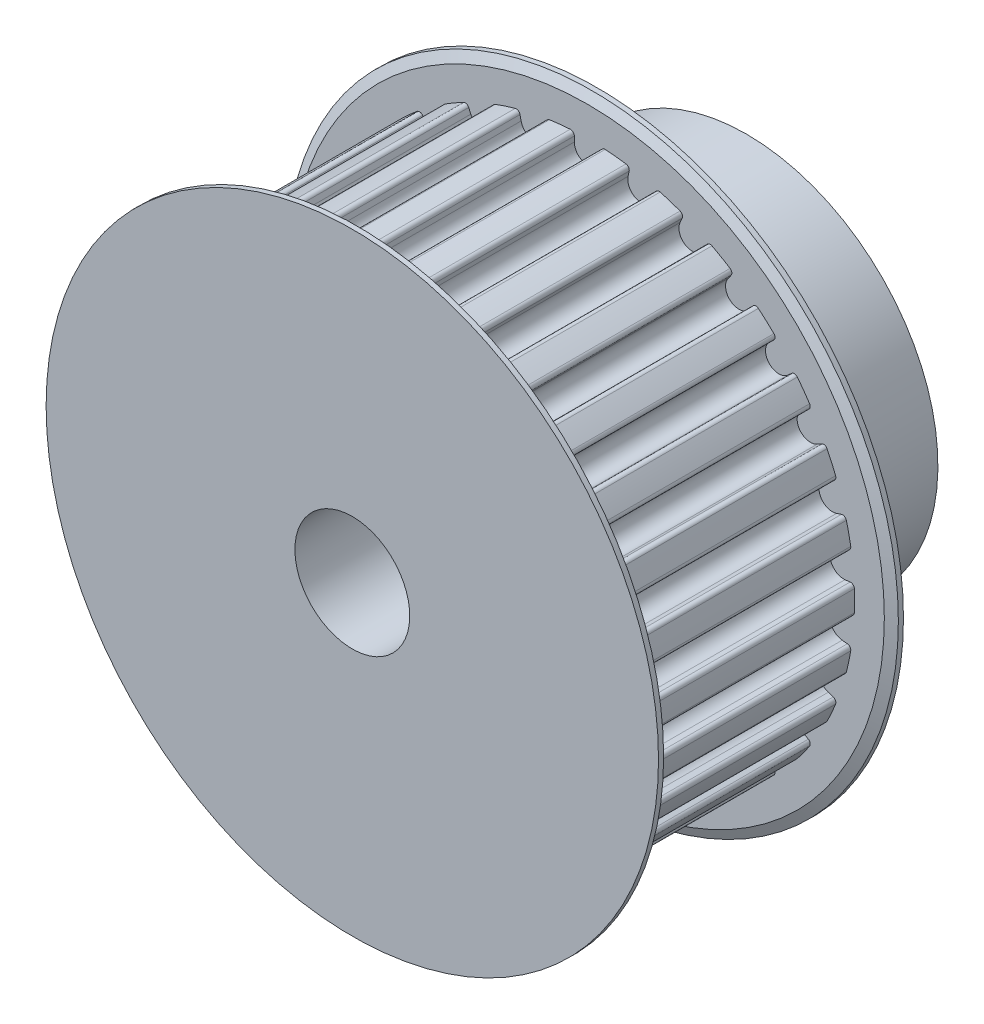
SolidWorks part; units mm, degrees
ref_plane "Front" through (0, 0, 0) normal (0, 0, 1) x (1, 0, 0)
ref_plane "Top" through (0, 0, 0) normal (0, 1, 0) x (1, 0, 0)
ref_plane "Right" through (0, 0, 0) normal (1, 0, 0) x (0, 0, -1)
sketch "support-front-body" plane through (0, 0, 0) normal (0, 0, 1) x (1, 0, 0)
  line L0 (0, 0) -> (0, 13.945) construction
  line L1 (0, 0) -> (0, -13.945) construction
  line L2 (0, 0) -> (13.945, 0) construction
  line L3 (0, 0) -> (-13.945, 0) construction
  circle A0 centre (0, 0) radius 13.945
  dimension "diam-outer" = 27.89
sketch "support-right-body" plane through (0, 0, 0) normal (1, 0, 0) x (0, 0, -1)
  line L0 (0, 0) -> (12.8, 0) construction
  line L1 (0, 13.945) -> (12.8, 13.945)
  line L2 (0, 13.945) -> (0, -13.945)
  line L3 (0, -13.945) -> (12.8, -13.945)
  line L4 (12.8, 13.945) -> (12.8, -13.945)
  dimension "length" = 12.8
sketch "support-right-chamfer" plane through (0, 0, 0) normal (1, 0, 0) x (0, 0, -1)
  line L0 (0, 0) -> (12.8, 0) construction
  line L1 (0, -13.945) -> (0, -12.945)
  line L2 (0, 13.945) -> (0, -13.945) construction
  line L4 (0, -12.945) -> (1, -13.945)
  line L5 (0, -13.945) -> (12.8, -13.945) construction
  line L7 (1, -13.945) -> (0, -13.945)
  line L9 (12.8, -13.945) -> (11.8, -13.945)
  line L11 (11.8, -13.945) -> (12.8, -12.945)
  line L12 (12.8, 13.945) -> (12.8, -13.945) construction
  line L14 (12.8, -12.945) -> (12.8, -13.945)
  dimension "height-chamfer-front" = 1
  dimension "angle-chamfer-front" = 45
  dimension "angle-chamfer-back" = 45
  dimension "height-chamfer-back" = 1
sketch "support-right-hub" plane through (0, 0, 0) normal (1, 0, 0) x (0, 0, -1)
  line L0 (20.6, 0) -> (12.8, 0) construction
  line L1 (12.8, 10) -> (20.6, 10)
  line L2 (12.8, 10) -> (12.8, -10)
  line L3 (12.8, -10) -> (20.6, -10)
  line L4 (20.6, 10) -> (20.6, -10)
  line L6 (0, 0) -> (12.8, 0) construction
  line L8 (0, 13.945) -> (0, -13.945) construction
  dimension "diam-hub" = 20
  dimension "length-hub" = 7.8
  dimension "dist-hub" = 12.8
sketch "support-right-bore" plane through (0, 0, 0) normal (1, 0, 0) x (0, 0, -1)
  line L0 (0, 13.945) -> (0, -13.945) construction
  line L1 (0, 3) -> (20.6, 3)
  line L2 (0, 3) -> (0, -3)
  line L3 (0, -3) -> (20.6, -3)
  line L4 (20.6, 3) -> (20.6, 0)
  line L5 (20.6, 0) -> (0, 0) construction
  line L6 (0, 0) -> (12.8, 0) construction
  line L7 (20.6, 0) -> (20.6, -3)
  line L8 (20.6, -3) -> (20.6, 3) construction
  dimension "diam-bore" = 6
  dimension "length-bore" = 20.6
  dimension "angle-bore-bottom" = 180
  dimension "angle-bore" = 90
sketch "support-stop-screw-hole" plane through (0, 0, 0) normal (1, 0, 0) x (0, 0, -1)
  line L1 (6.5667, 11) -> (9.4333, 11)
  line L2 (6.5667, 11) -> (6.5667, -1)
  line L3 (8, -1) -> (9.4333, -1)
  line L4 (9.4333, 11) -> (9.4333, -1)
  line L5 (8, -1) -> (8, 11) construction
  line L6 (8, -1) -> (6.5667, -1)
  line L7 (0, 0) -> (8, 0) construction
  line L8 (0, 13.945) -> (0, -13.945) construction
  dimension "diam-stop-screw-hole" = 2.8665
  dimension "dist-stop-screw-hole" = 8
  dimension "depth-stop-screw-hole" = 12
  dimension "angle-stop-screw-hole" = 180
  dimension "height-stop-screw-hole" = 11
sketch "support-front-keygroove" plane through (0, 0, 0) normal (0, 0, 1) x (1, 0, 0)
  line L0 (0, 0) -> (0, -3) construction
  line L1 (-1, 5) -> (1, 5)
  line L2 (-1, 5) -> (-1, 2.8)
  line L3 (-1, 2.8) -> (1, 2.8)
  line L4 (1, 5) -> (1, 2.8)
  line L5 (0, 0) -> (0, 3) construction
  circle A0 centre (0, 0) radius 3 construction
  dimension "width-keygroove" = 2
  dimension "dist-keygroove" = 8
  dimension "height-keygroove" = 2.2
sketch "support-front-tooth" plane through (0, 0, 0) normal (0, 0, 1) x (1, 0, 0)
  line L0 (0.7, 13.445) -> (0.7, 13.7155)
  line L1 (0, 0) -> (0, 13.945) construction
  line L2 (-0.7, 13.445) -> (-0.7, 13.7155)
  line L3 (0, 13.9151) -> (0, 13.945) construction
  line L8 (0, 13.9151) -> (0, 12.745) construction
  line L9 (0.9131, 13.9151) -> (-0.9131, 13.9151) construction
  line L10 (0, 13.9151) -> (0, 15.0851) construction
  line L17 (0.9131, 13.9151) -> (0.9131, 15.0851)
  line L21 (-0.9131, 15.0851) -> (-0.9131, 13.9151)
  line L22 (0.9131, 15.0851) -> (-0.9131, 15.0851)
  arc A0 (-0.7, 13.445) -> (0.7, 13.445) centre (0, 13.445) ccw
  circle A1 centre (0, 0) radius 13.945 construction
  arc A2 (0.7, 13.7155) -> (0.9131, 13.9151) centre (0.9, 13.7155) cw
  arc A3 (-0.7, 13.7155) -> (-0.9131, 13.9151) centre (-0.9, 13.7155) ccw
  circle A4 centre (0, 0) radius 13.945
  dimension "D3" = 0.2
  dimension "D2" = 0.7
  dimension "D1" = 1.2
sketch "support-right-flange" plane through (0, 0, 0) normal (1, 0, 0) x (0, 0, -1)
  line L0 (0, 6.9795) -> (0, 12.9932)
  line L1 (12.8, 13.945) -> (12.8, -13.945) construction
  line L2 (0, 12.9932) -> (0.5, 12.9932) construction
  line L3 (0.5, 12.9932) -> (0.5, 16)
  line L4 (0, 16) -> (0.5, 16)
  line L5 (0.5, 12.9932) -> (0.5, 6.9795)
  line L6 (0.5, 6.9795) -> (0, 6.9795)
  line L7 (6.4, 13.945) -> (6.4, 0) construction
  line L8 (0, 13.945) -> (12.8, 13.945) construction
  line L9 (0, 12.9932) -> (0, 16)
  line L10 (12.3, 6.9795) -> (12.8, 6.9795)
  line L11 (12.3, 12.9932) -> (12.3, 6.9795)
  line L12 (12.8, 16) -> (12.3, 16)
  line L13 (12.3, 12.9932) -> (12.3, 16)
  line L14 (12.8, 12.9932) -> (12.8, 16)
  line L15 (12.8, 6.9795) -> (12.8, 12.9932)
  line L16 (12.8, 0) -> (0, 0) construction
  line L17 (12.8, -6.9795) -> (12.8, -12.9932)
  line L18 (12.8, -12.9932) -> (12.8, -16)
  line L19 (12.3, -12.9932) -> (12.3, -16)
  line L20 (12.8, -16) -> (12.3, -16)
  line L21 (12.3, -12.9932) -> (12.3, -6.9795)
  line L22 (12.3, -6.9795) -> (12.8, -6.9795)
  line L23 (0.5, -6.9795) -> (0, -6.9795)
  line L24 (0.5, -12.9932) -> (0.5, -6.9795)
  line L25 (0, -16) -> (0.5, -16)
  line L26 (0.5, -12.9932) -> (0.5, -16)
  line L27 (0, -12.9932) -> (0, -16)
  line L28 (0, -6.9795) -> (0, -12.9932)
  line L29 (0, 0) -> (12.8, 0) construction
  line L30 (0, 12.9932) -> (0.5, 12.9932) construction
  line L31 (0.25, 6.9795) -> (0.25, 9.9863) construction
  line L32 (0.25, 9.9863) -> (0.25, 12.9932) construction
  line L33 (0.25, 16) -> (0.25, 12.9932) construction
  line L34 (0, 13.945) -> (12.8, 13.945) construction
  dimension "angle-flange" = 180
  dimension "thickness-flange" = 0.5
  dimension "diam-flange-inner" = 13.959
  dimension "diam-flange-outer" = 32
  dimension "width-flange-inner" = 11.8
sketch "support-right-flange-profile" plane through (0, 0, 0) normal (1, 0, 0) x (0, 0, -1)
  line L0 (0.2668, 16) -> (0.5, 16)
  line L2 (0.5, 16) -> (0.5, 15.5)
  line L3 (0.5, 12.9932) -> (0.5, 6.9795) construction
  line L4 (0.5, 15.5) -> (0.2668, 16)
  line L5 (0, 0) -> (12.8, 0) construction
  line L6 (6.4, 0) -> (6.4, 13.945) construction
  line L7 (12.3, 15.5) -> (12.5332, 16)
  line L8 (12.3, 16) -> (12.3, 15.5)
  line L9 (12.5332, 16) -> (12.3, 16)
  dimension "D1" = 25
  dimension "D2" = 0.5
ref_axis "ref-axis-center" through (0, 0, -12.8) along (0, 0, 1)
ref_plane "ref-plane-front" through (0, 0, 0) normal (0, 0, 1) x (1, 0, 0)
ref_plane "ref-plane-back" through (0, 0, -12.8) normal (0, 0, 1) x (1, 0, 0)
ref_plane "ref-plane-hub-front" through (0, 0, -12.8) normal (0, 0, 1) x (1, 0, 0)
ref_plane "ref-plane-hub-back" through (0, 0, -20.6) normal (0, 0, 1) x (1, 0, 0)
ref_plane "ref-plane-bore-front" through (0, 0, 0) normal (0, 0, 1) x (1, 0, 0)
ref_plane "ref-plane-bore-back" through (0, 0, -20.6) normal (0, 0, 1) x (1, 0, 0)
ref_plane "ref-plane-stop-screw-hole-top" through (0, 11, 0) normal (0, 1, 0) x (-1, 0, 0)
ref_axis "ref-axis-stop-screw-hole" through (0, 11, -8) along (0, -1, 0)
sketch "Sketch5" plane through (0, 0, 0) normal (1, 0, 0) x (0, 0, -1)
  line L0 (12.8, 13.945) -> (12.8, -13.945) construction
  line L1 (0, 13.945) -> (12.8, 13.945) construction
  line L2 (0, 13.945) -> (0, -13.945) construction
  line L3 (0, 0) -> (12.8, 0) construction
  line L4 (12.8, 13.945) -> (12.8, 0)
  line L5 (0, 13.945) -> (12.8, 13.945)
  line L6 (0, 13.945) -> (0, 0)
  line L7 (0, 0) -> (12.8, 0) construction
  line L8 (0, 0) -> (12.8, 0)
  dimension "D1" = 12.8
revolve "body" add sketch "Sketch5" angle 360 about L7
sketch "Sketch11" plane through (0, 0, 0) normal (1, 0, 0) x (0, 0, -1)
  line L0 (0, -13.945) -> (0, -12.945) construction
  line L3 (1, -13.945) -> (0, -13.945) construction
  line L5 (0, -12.945) -> (1, -13.945) construction
  line L8 (0, -13.945) -> (0, -12.945)
  line L9 (1, -13.945) -> (0, -13.945)
  line L10 (0, -12.945) -> (1, -13.945)
  line L11 (0, 0) -> (12.8, 0) construction
  line L12 (0, 0) -> (12.8, 0) construction
revolve "cut-chamfer-front" [suppressed] cut sketch "Sketch11" angle 360 about L12
sketch "Sketch13" plane through (0, 0, 0) normal (1, 0, 0) x (0, 0, -1)
  line L0 (0, 0) -> (12.8, 0) construction
  line L1 (12.8, -13.945) -> (11.8, -13.945) construction
  line L2 (12.8, -12.945) -> (12.8, -13.945) construction
  line L3 (11.8, -13.945) -> (12.8, -12.945) construction
  line L4 (0, 0) -> (12.8, 0) construction
  line L5 (12.8, -13.945) -> (11.8, -13.945)
  line L6 (12.8, -12.945) -> (12.8, -13.945)
  line L7 (11.8, -13.945) -> (12.8, -12.945)
revolve "cut-chamfer-back" [suppressed] cut sketch "Sketch13" angle 360 about L4
sketch "Sketch16" plane through (0, 0, 0) normal (1, 0, 0) x (0, 0, -1)
  line L0 (20.6, 10) -> (20.6, -10) construction
  line L1 (12.8, 10) -> (20.6, 10) construction
  line L2 (20.6, 0) -> (12.8, 0) construction
  line L3 (12.8, 10) -> (12.8, -10) construction
  line L4 (20.6, 10) -> (20.6, 0)
  line L5 (12.8, 10) -> (20.6, 10)
  line L6 (20.6, 0) -> (12.8, 0) construction
  line L7 (12.8, 10) -> (12.8, 0)
  line L8 (20.6, 0) -> (12.8, 0)
revolve "body-hub" add sketch "Sketch16" angle 360 about L6
sketch "Sketch17" plane through (0, 0, 0) normal (1, 0, 0) x (0, 0, -1)
  line L0 (20.6, 3) -> (20.6, 0) construction
  line L1 (20.6, 0) -> (0, 0) construction
  line L2 (0, 3) -> (20.6, 3) construction
  line L3 (0, 3) -> (0, -3) construction
  line L4 (20.6, 3) -> (20.6, 0)
  line L5 (20.6, 0) -> (0, 0) construction
  line L6 (0, 3) -> (20.6, 3)
  line L7 (0, 3) -> (0, 0)
  line L8 (20.6, 0) -> (0, 0)
revolve "body-bore" cut sketch "Sketch17" angle 360 about L5
sketch "Sketch19" plane through (0, 0, 0) normal (1, 0, 0) x (0, 0, -1)
  line L0 (6.5667, 11) -> (9.4333, 11) construction
  line L1 (8, -1) -> (8, 11) construction
  line L2 (9.4333, 11) -> (9.4333, -1) construction
  line L3 (8, -1) -> (9.4333, -1) construction
  line L4 (8, 11) -> (9.4333, 11)
  line L5 (8, -1) -> (8, 11) construction
  line L6 (9.4333, 11) -> (9.4333, -1)
  line L7 (8, -1) -> (9.4333, -1)
  line L8 (8, -1) -> (8, 11)
revolve "body-stop-screw-hole" [suppressed] cut sketch "Sketch19" angle 360 about L5
pattern_circular "pattern-stop-screw-hole" [suppressed] count 2 every 90 about axis through (0, 0, -12.8) along (0, 0, 1) reverse direction yes
sketch "Sketch21" plane through (0, 0, 0) normal (0, 0, 1) x (1, 0, 0)
  line L0 (-1, 5) -> (1, 5) construction
  line L1 (-1, 5) -> (-1, 2.8) construction
  line L2 (-1, 2.8) -> (1, 2.8) construction
  line L3 (1, 5) -> (1, 2.8) construction
  line L4 (-1, 5) -> (1, 5)
  line L5 (-1, 5) -> (-1, 2.8)
  line L6 (-1, 2.8) -> (1, 2.8)
  line L7 (1, 5) -> (1, 2.8)
extrude "cut-keygroove" [suppressed] cut sketch "Sketch21" against normal up to surface (17.5 mm away)
sketch "Sketch23" plane through (0, 0, 0) normal (0, 0, 1) x (1, 0, 0)
  line L5 (0.7, 13.445) -> (0.7, 13.7155)
  line L6 (0.7, 13.445) -> (0.7, 13.7155)
  line L7 (-0.7, 13.7155) -> (-0.7, 13.445)
  line L8 (-0.7, 13.7155) -> (-0.7, 13.445)
  line L9 (0.9131, 13.9151) -> (0.9131, 15.0851)
  line L13 (-0.9131, 15.0851) -> (-0.9131, 13.9151)
  line L14 (0.9131, 15.0851) -> (-0.9131, 15.0851)
  line L15 (0.9131, 13.9151) -> (0.9131, 15.0851)
  line L19 (-0.9131, 15.0851) -> (-0.9131, 13.9151)
  line L20 (0.9131, 15.0851) -> (-0.9131, 15.0851)
  arc A3 (0.9131, 13.9151) -> (0.7, 13.7155) centre (0.9, 13.7155) ccw
  arc A4 (0.9131, 13.9151) -> (0.7, 13.7155) centre (0.9, 13.7155) ccw
  arc A5 (-0.7, 13.445) -> (0.7, 13.445) centre (0, 13.445) ccw
  arc A6 (-0.7, 13.445) -> (0.7, 13.445) centre (0, 13.445) ccw
  arc A7 (-0.7, 13.7155) -> (-0.9131, 13.9151) centre (-0.9, 13.7155) ccw
  arc A8 (-0.7, 13.7155) -> (-0.9131, 13.9151) centre (-0.9, 13.7155) ccw
  dimension "D1" = 0
extrude "cut-tooth" cut sketch "Sketch23" against normal up to surface (12.8 mm away) up to plane "ref-plane-back"
pattern_circular "pattern-tooth" count 30 over 360 about axis through (0, 0, -12.8) along (0, 0, 1) of "cut-tooth"
sketch "Sketch25" plane through (0, 0, 0) normal (1, 0, 0) x (0, 0, -1)
  line L0 (0, 0) -> (12.8, 0) construction
  line L1 (0.5, 6.9795) -> (0, 6.9795) construction
  line L2 (0.5, 12.9932) -> (0.5, 6.9795) construction
  line L4 (0, 16) -> (0.5, 16) construction
  line L5 (0, 12.9932) -> (0, 16) construction
  line L6 (0, 6.9795) -> (0, 12.9932) construction
  line L7 (0, 0) -> (12.8, 0) construction
  line L8 (0.5, 6.9795) -> (0, 6.9795)
  line L9 (0.5, 12.9932) -> (0.5, 6.9795)
  line L10 (0, 16) -> (0.5, 16)
  line L11 (0.5, 12.9932) -> (0.5, 16) construction
  line L12 (0, 12.9932) -> (0, 16)
  line L13 (0, 6.9795) -> (0, 12.9932)
  line L14 (0.5, 12.9932) -> (0.5, 16)
revolve "body-flange-front" add sketch "Sketch25" angle 360 about L7
sketch "Sketch26" plane through (0, 0, 0) normal (1, 0, 0) x (0, 0, -1)
  line L0 (12.8, 0) -> (0, 0) construction
  line L1 (12.3, 6.9795) -> (12.8, 6.9795) construction
  line L2 (12.3, 12.9932) -> (12.3, 6.9795) construction
  line L4 (12.8, 16) -> (12.3, 16) construction
  line L5 (12.8, 12.9932) -> (12.8, 16) construction
  line L6 (12.8, 6.9795) -> (12.8, 12.9932) construction
  line L7 (12.8, 0) -> (0, 0) construction
  line L8 (12.3, 6.9795) -> (12.8, 6.9795)
  line L9 (12.3, 12.9932) -> (12.3, 6.9795)
  line L10 (12.8, 16) -> (12.3, 16)
  line L11 (12.3, 12.9932) -> (12.3, 16) construction
  line L12 (12.8, 12.9932) -> (12.8, 16)
  line L13 (12.8, 6.9795) -> (12.8, 12.9932)
  line L14 (12.3, 12.9932) -> (12.3, 16)
revolve "body-flange-back" add sketch "Sketch26" angle 360 about L7
sketch "Sketch28" plane through (0, 0, 0) normal (1, 0, 0) x (0, 0, -1)
  line L0 (0.5, 16) -> (0.5, 15.5) construction
  line L1 (0.2668, 16) -> (0.5, 16) construction
  line L2 (0.5, 15.5) -> (0.2668, 16) construction
  line L3 (0.5, 16) -> (0.5, 15.5)
  line L4 (0.2668, 16) -> (0.5, 16)
  line L5 (0.5, 15.5) -> (0.2668, 16)
  line L6 (12.8, 0) -> (0, 0) construction
  line L7 (12.8, 0) -> (0, 0) construction
revolve "body-flange-profile-front" cut sketch "Sketch28" angle 360 about L7
sketch "Sketch29" plane through (0, 0, 0) normal (1, 0, 0) x (0, 0, -1)
  line L0 (12.8, 0) -> (0, 0) construction
  line L1 (12.3, 16) -> (12.3, 15.5) construction
  line L2 (12.5332, 16) -> (12.3, 16) construction
  line L3 (12.3, 15.5) -> (12.5332, 16) construction
  line L4 (12.8, 0) -> (0, 0) construction
  line L5 (12.3, 16) -> (12.3, 15.5)
  line L6 (12.5332, 16) -> (12.3, 16)
  line L7 (12.3, 15.5) -> (12.5332, 16)
revolve "body-flange-profile-back" cut sketch "Sketch29" angle 360 about L4
sketch "support-right-cut-body" plane through (0, 0, 0) normal (1, 0, 0) x (0, 0, -1)
  line L0 (12.8, 13.945) -> (12.8, -13.945) construction
  line L1 (0, 13.945) -> (12.8, 13.945) construction
  line L2 (0, 13.945) -> (0, -13.945) construction
  line L3 (0, -13.945) -> (12.8, -13.945) construction
  line L4 (12.8, 13.945) -> (12.8, -13.945) construction
  line L5 (0, 13.945) -> (0, -13.945) construction
  line L6 (0, 13.945) -> (12.8, 13.945) construction
  line L7 (0, -13.945) -> (12.8, -13.945) construction
  line L8 (12.8, 0) -> (0, 0) construction
  line L9 (6.4, 13.945) -> (6.4, -13.945) construction
  line L10 (12.8, 11.8117) -> (8.5333, 11.8117)
  line L11 (12.8, 11.8117) -> (12.8, -11.8117)
  line L12 (12.8, -11.8117) -> (8.5333, -11.8117)
  line L13 (8.5333, 11.8117) -> (8.5333, -11.8117)
  line L14 (0, 11.8117) -> (4.2667, 11.8117)
  line L15 (0, 11.8117) -> (0, -11.8117)
  line L16 (0, -11.8117) -> (4.2667, -11.8117)
  line L17 (4.2667, 11.8117) -> (4.2667, -11.8117)
  line L18 (8.5333, 11.8117) -> (4.2667, 11.8117) construction
  line L19 (4.2667, -11.8117) -> (6.4, -11.8117) construction
  line L20 (4.2667, -11.8117) -> (4.2667, -13.945) construction
  line L21 (12.8, 10) -> (8.5333, 10)
  line L23 (12.8, 10) -> (20.6, 10) construction
  line L24 (12.8, -10) -> (8.5333, -10)
  line L25 (0, 10) -> (4.2667, 10)
  line L26 (0, -10) -> (4.2667, -10)
sketch "Sketch31" plane through (0, 0, 0) normal (1, 0, 0) x (0, 0, -1)
  line L0 (0, 11.8117) -> (0, -11.8117) construction
  line L1 (0, 11.8117) -> (4.2667, 11.8117) construction
  line L2 (4.2667, 11.8117) -> (4.2667, -11.8117) construction
  line L3 (12.8, 11.8117) -> (12.8, -11.8117) construction
  line L4 (12.8, 11.8117) -> (8.5333, 11.8117) construction
  line L5 (8.5333, 11.8117) -> (8.5333, -11.8117) construction
  line L7 (0, 11.8117) -> (0, 10)
  line L8 (0, 11.8117) -> (4.2667, 11.8117)
  line L9 (4.2667, 11.8117) -> (4.2667, 10)
  line L10 (12.8, 11.8117) -> (12.8, 10)
  line L11 (12.8, 11.8117) -> (8.5333, 11.8117)
  line L12 (8.5333, 11.8117) -> (8.5333, 10)
  line L13 (12.8, 10) -> (8.5333, 10)
  line L14 (12.8, 10) -> (8.5333, 10) construction
  line L15 (4.2667, 10) -> (0, 10)
  line L16 (0, 0) -> (12.8, 0) construction
  line L17 (12.8, 0) -> (0, 0) construction
revolve "cut-body" [suppressed] cut sketch "Sketch31" angle 360 about L16
sketch "草图1" plane through (0, 0, 0) normal (0, 1, 0) x (1, 0, 0)
  line L0 (10, 20.6) -> (-10, 20.6) construction
  circle A0 centre (0, 17.1) radius 1
  dimension "D1" = 2
  dimension "D2" = 2
  dimension "D3" = 2
  dimension "D4" = 3.5
extrude "切除-拉伸1" cut sketch "草图1" against normal blind 18
